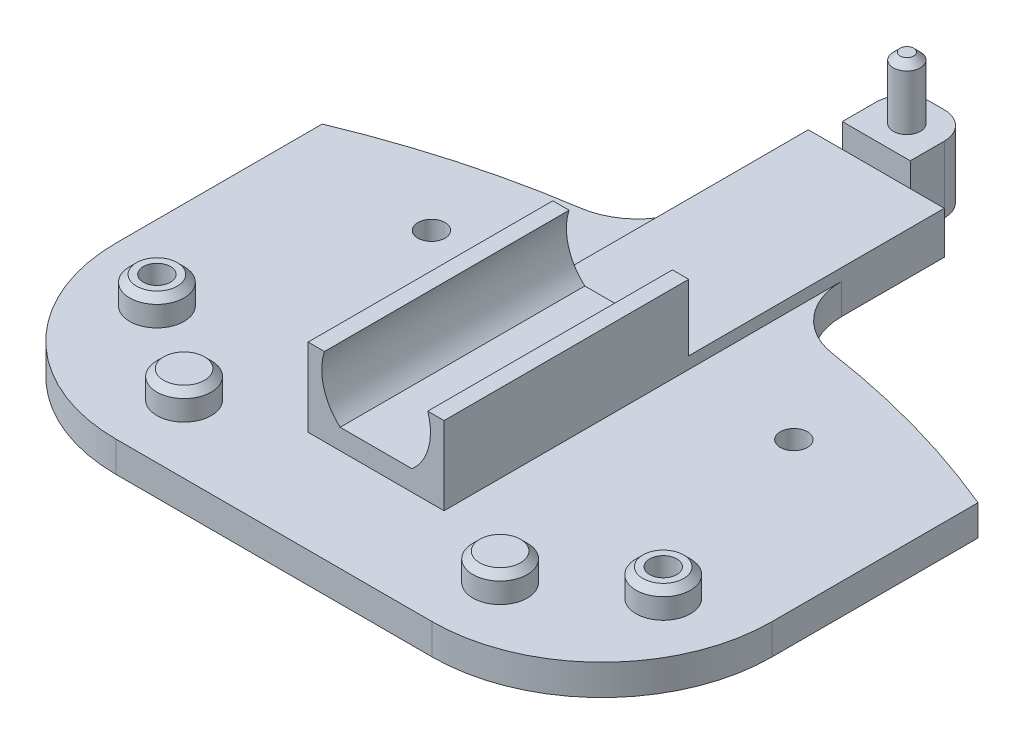
SolidWorks part; units mm, degrees
ref_plane "Front Plane" through (0, 0, 0) normal (0, 0, 1) x (1, 0, 0)
ref_plane "Top Plane" through (0, 0, 0) normal (0, 1, 0) x (1, 0, 0)
ref_plane "Right Plane" through (0, 0, 0) normal (1, 0, 0) x (0, 0, -1)
sketch "Sketch1" plane through (0, 0, 0) normal (0, 1, 0) x (1, 0, 0)
  line L1 (0, 0) -> (96.5, 0)
  line L2 (0, 0) -> (0, -110)
  line L3 (0, -110) -> (96.5, -110)
  line L4 (96.5, 0) -> (96.5, -110)
  dimension "D1" = 110
  dimension "D2" = 96.5
extrude "Boss-Extrude1" add sketch "Sketch1" along normal blind 4.5
sketch "Sketch2" plane through (0, 4.5, 0) normal (0, 1, 0) x (1, 0, 0)
  line L0 (48.25, -8.0497) -> (48.25, 8.0497) construction
  line L1 (85.5, -100) -> (85.5, -90) construction
  line L2 (-30.7875, -55) -> (30.7875, -55) construction
  line L3 (71.5, -100) -> (85.5, -100) construction
  line L4 (0, 0) -> (25, 0) construction
  line L5 (96.5, 0) -> (0, 0) construction
  line L6 (25, 0) -> (25, -100) construction
  line L7 (25, -100) -> (11, -100) construction
  line L8 (11, -100) -> (11, -90) construction
  line L9 (71.5, 0) -> (71.5, -100) construction
  line L10 (96.5, 0) -> (71.5, 0) construction
  line L11 (0, 0) -> (0, -110) construction
  circle A0 centre (25, -100) radius 4
  circle A1 centre (11, -90) radius 4
  circle A2 centre (85.5, -90) radius 4
  circle A3 centre (71.5, -100) radius 4
  point P3 (48.25, 0)
  point P6 (0, -55)
  dimension "D3" = 8
  dimension "D5" = 8
  dimension "D1" = 25
  dimension "D2" = 100
  dimension "D4" = 14
  dimension "D6" = 10
  dimension "D7" = 48.25
extrude "Boss-Extrude2" add sketch "Sketch2" along normal blind 4 contours A0 | A3 region at (25, 4.5, 100) region at (71.5, 4.5, 100)
sketch "Sketch3" plane through (0, 4.5, 0) normal (0, 1, 0) x (1, 0, 0)
  line L0 (71.5, -100) -> (71.5, -12.4) construction
  line L1 (48.25, 0) -> (48.25, -50000) construction
  line L2 (96.5, 0) -> (0, 0) construction
  line L3 (71.5, -12.4) -> (48.25, -12.4) construction
  line L4 (48.25, -12.4) -> (48.25, -14.9) construction
  circle A0 centre (48.25, -16.9) radius 2
  point P7 (48.25, 0)
  dimension "D2" = 4
  dimension "D1" = 87.6
  dimension "D3" = 2.5
extrude "Boss-Extrude3" add sketch "Sketch3" along normal blind 14.4
sketch "Sketch4" plane through (0, 4.5, 0) normal (0, 1, 0) x (1, 0, 0)
  line L0 (48.25, -18.9) -> (48.25, -21.4) construction
  line L1 (48.25, -14.9) -> (48.25, -12.4) construction
  line L2 (48.25, -21.4) -> (38.25, -21.4)
  line L3 (48.25, -21.4) -> (48.25, -59)
  line L4 (48.25, -59) -> (38.25, -59)
  line L5 (38.25, -21.4) -> (38.25, -59)
  line L6 (48.25, -21.4) -> (38.25, -59) construction
  line L7 (48.25, -59) -> (38.25, -21.4) construction
  line L8 (48.25, -59) -> (58.25, -59)
  line L9 (48.25, -59) -> (48.25, -23)
  line L12 (48.25, -21.4) -> (53.25, -21.4)
  line L13 (53.25, -21.4) -> (53.25, -16.4)
  line L14 (38.25, -59) -> (58.25, -59)
  line L15 (38.25, -59) -> (38.25, -95)
  line L16 (38.25, -95) -> (58.25, -95)
  line L17 (58.25, -59) -> (58.25, -95)
  line L18 (38.25, -59) -> (58.25, -95) construction
  line L19 (38.25, -95) -> (58.25, -59) construction
  line L21 (48.25, -12.4) -> (47.25, -12.4)
  line L22 (48.25, -12.4) -> (48.25, -21.4)
  line L23 (48.25, -21.4) -> (43.25, -21.4)
  line L24 (43.25, -16.4) -> (43.25, -21.4)
  line L25 (48.25, -12.4) -> (43.25, -21.4) construction
  line L26 (48.25, -21.4) -> (43.25, -12.4) construction
  line L27 (48.25, -12.4) -> (49.25, -12.4)
  line L28 (48.25, -12.4) -> (48.25, -23)
  line L31 (48.25, -21.4) -> (58.25, -21.4)
  line L32 (48.25, -21.4) -> (48.25, -59)
  line L33 (48.25, -59) -> (58.25, -59)
  line L34 (58.25, -21.4) -> (58.25, -59)
  line L35 (48.25, -21.4) -> (58.25, -59) construction
  line L36 (48.25, -59) -> (58.25, -21.4) construction
  circle A0 centre (48.25, -16.9) radius 2 construction
  circle A1 centre (48.25, -16.9) radius 2 construction
  arc A2 (49.25, -12.4) -> (53.25, -16.4) centre (49.25, -16.4) cw
  arc A3 (43.25, -16.4) -> (47.25, -12.4) centre (47.25, -16.4) cw
  point P8 (43.25, -40.2)
  point P16 (48.25, -77)
  point P24 (45.75, -16.9)
  point P28 (50.75, -17.7)
  point P35 (53.25, -40.2)
  circle M2 centre (48.25, -16.9) radius 2
  dimension "D3" = 4
  dimension "D1" = 2.5
  dimension "D2" = 2.5
  dimension "D4" = 37.6
  dimension "D5" = 36
  dimension "D6" = 20
extrude "Boss-Extrude4" add sketch "Sketch4" along normal blind 1.75 contours L2 L5 L4 L3 | L8 L3 region at (43.25, 4.5, 40.2) region at (53.25, 4.5, 40.2)
extrude "Boss-Extrude5" add sketch "Sketch4<3>" along normal blind 11.5 contours L17 L8 L4 L15 L16 region at (48.25, 4.5, 77)
sketch "Sketch4<3>" plane through (0, 4.5, 0) normal (0, 1, 0) x (1, 0, 0) same geometry as "Sketch4"
extrude "Boss-Extrude6" add sketch "Sketch4<5>" along normal blind 5.3 contours A3 L24 L2 L22 L21 M2 | A2 L27 L22 M2 region at (50.8877, 4.5, 17.251) region at (45.6123, 4.5, 17.251)
sketch "Sketch4<5>" plane through (0, 4.5, 0) normal (0, 1, 0) x (1, 0, 0) same geometry as "Sketch4"
chamfer "Chamfer2" distance 1 angle 45 1 edges at (48.25, 18.9, 18.9)
sketch "Sketch9" plane through (0, 0, 59) normal (0, 0, -1) x (-1, 0, 0)
  line L0 (-58.25, 6.25) -> (-58.25, 7.5) construction
  line L4 (-58.25, 7.5) -> (-50058.25, 7.5) construction
  line L7 (-64.0844, 7.5) -> (-64.0844, 19.5) construction
  line L10 (-64.0844, 19.5) -> (-50064.0844, 19.5) construction
  line L11 (-64.0844, 13.5) -> (49935.9156, 13.5) construction
  line L12 (-58.25, 4.5) -> (-38.25, 4.5) construction
  line L13 (-48.25, 4.5) -> (-48.25, 50004.5) construction
  line L14 (-58.25, 16) -> (-58.25, 6.25) construction
  line L16 (-53.5415, 7.5) -> (-42.9585, 7.5)
  circle A0 centre (-48.25, 13.5) radius 8
  point P15 (-64.0844, 13.5)
  point P22 (-48.25, 4.5)
  line M5 (-38.25, 16) -> (-58.25, 16)
  dimension "D3" = 16
  dimension "D1" = 1.25
  dimension "D2" = 12
extrude "Cut-Extrude6" cut sketch "Sketch9" against normal through all contours A0 L16 M5 region at (48.25, 11.9541, 59)
chamfer "Chamfer3" distance 1 angle 45 2 edges at (71.5, 8.5, 104) (25, 8.5, 104)
extrude "Boss-Extrude8" add sketch "Sketch2<4>" along normal blind 4 contours A1 | A2 region at (11, 4.5, 90) region at (85.5, 4.5, 90)
sketch "Sketch2<4>" plane through (0, 4.5, 0) normal (0, 1, 0) x (1, 0, 0) same geometry as "Sketch2"
sketch "Sketch20" plane through (0, 4.5, 0) normal (0, 1, 0) x (1, 0, 0)
  line L0 (0, 0) -> (96.5, 0)
  line L1 (96.5, 0) -> (96.5, -54.6877)
  line L2 (0, 0) -> (0, -54.6877)
  line L3 (38.25, -45.4006) -> (38.25, -21.4)
  line L4 (38.25, -21.4) -> (43.25, -21.4)
  line L5 (43.25, -21.4) -> (43.25, -16.4)
  line L6 (47.25, -12.4) -> (49.25, -12.4)
  line L7 (53.25, -16.4) -> (53.25, -21.4)
  line L8 (53.25, -21.4) -> (58.25, -21.4)
  line L9 (58.25, -21.4) -> (58.25, -45.4006)
  arc A2 (0, -54.6877) -> (38.25, -45.4006) centre (48.25, -170) cw
  arc A3 (58.25, -45.4006) -> (96.5, -54.6877) centre (48.25, -170) cw
  arc A4 (43.25, -16.4) -> (47.25, -12.4) centre (47.25, -16.4) cw
  arc A5 (49.25, -12.4) -> (53.25, -16.4) centre (49.25, -16.4) cw
  circle A6 centre (48.25, -170) radius 125 construction
extrude "Cut-Extrude10" cut sketch "Sketch20" against normal through all
fillet "Fillet1" radius 10 2 edges at (58.25, 2.25, 45.4006) (38.25, 2.25, 45.4006)
sketch "Sketch21" plane through (0, 4.5, 0) normal (0, 1, 0) x (1, 0, 0)
  line L0 (38.25, -21.4) -> (38.25, -59) construction
  line L1 (18.7572, -48.5291) -> (21.5885, -60.1903)
  line L2 (48.25, -80) -> (48.25, 49920) construction
  circle A0 centre (21.5885, -60.1903) radius 2
  arc A1 (0, -54.6877) -> (38.25, -45.4006) centre (48.25, -170) cw
  circle A2 centre (48.25, -170) radius 125 construction
  circle A3 centre (74.9115, -60.1903) radius 2
  dimension "D1" = 4
  dimension "D2" = 12
extrude "Cut-Extrude11" cut sketch "Sketch21" against normal through all contours A0 | A3 region at (20.3873, 4.5, 61.7181) region at (74.9115, 4.5, 60.1903)
chamfer "Chamfer4" distance 1 angle 45 2 edges at (85.5, 8.5, 94) (11, 8.5, 94)
sketch "Sketch22" plane through (0, 8.5, 0) normal (0, 1, 0) x (1, 0, 0)
  circle A0 centre (11, -90) radius 2
  circle A1 centre (85.5, -90) radius 2
  dimension "D1" = 4
  dimension "D2" = 4
extrude "Cut-Extrude12" cut sketch "Sketch22" against normal through all
fillet "Fillet2" radius 25 2 edges at (96.5, 2.25, 110) (0, 2.25, 110)
